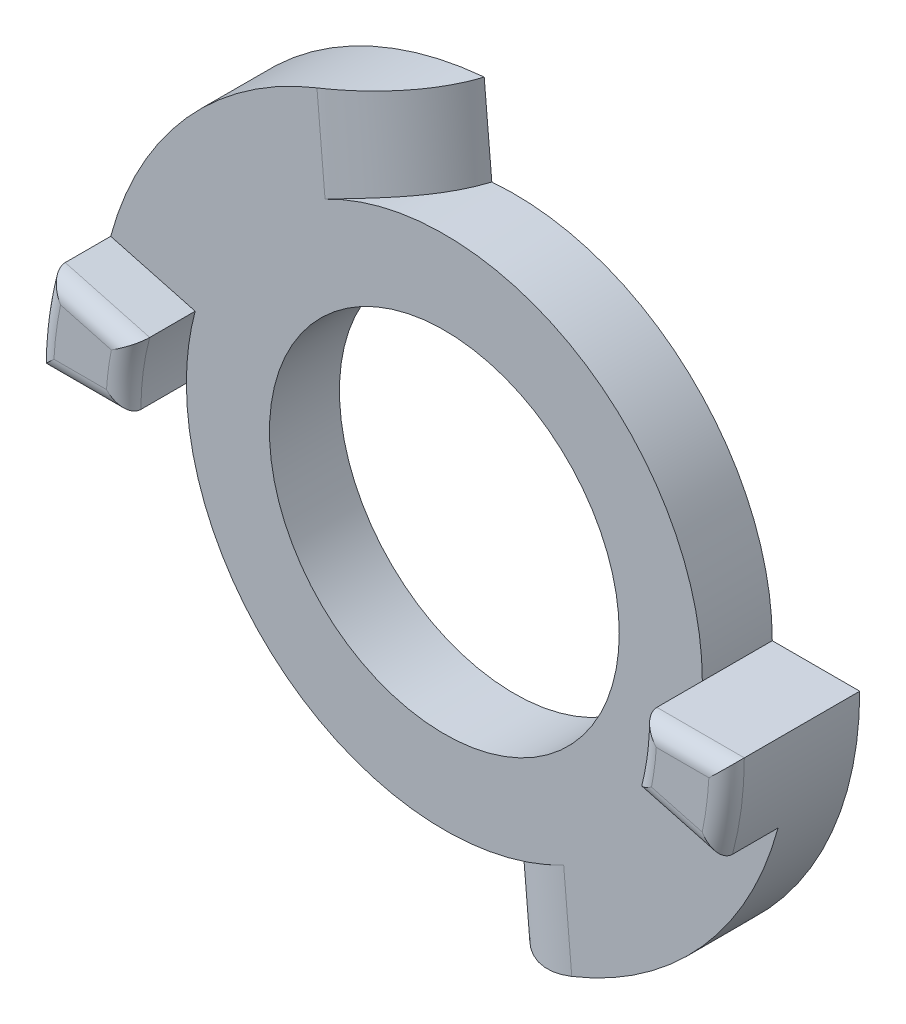
SolidWorks part; units mm, degrees
ref_plane "Front Plane" through (0, 0, 0) normal (0, 0, 1) x (1, 0, 0)
ref_plane "Top Plane" through (0, 0, 0) normal (0, 1, 0) x (1, 0, 0)
ref_plane "Right Plane" through (0, 0, 0) normal (1, 0, 0) x (0, 0, -1)
sketch "Sketch2" plane through (0, 0, 0) normal (0, 0, 1) x (1, 0, 0)
  line L0 (0, 0) -> (-0.9273, 10.599)
  line L1 (0, 7.5) -> (0, 10) construction
  line L2 (0, 0) -> (1.0257, -11.7238)
  line L3 (0, -7.5) -> (0, -10) construction
  line L4 (-10, 0) -> (0, 0)
  line L5 (0, 0) -> (10.8115, 0)
  circle A1 centre (0, 0) radius 9.875
  circle A2 centre (0, 0) radius 5
  circle A3 centre (0, 0) radius 7.375
  arc A4 (0, 10) -> (-10, 0) centre (0, 0) ccw construction
  line M6 (3.4641, -6) -> (-3.4641, -6)
  line M7 (-3.4641, -6) -> (-6.9282, 0)
  line M8 (-6.9282, 0) -> (-3.4641, 6)
  line M9 (-3.4641, 6) -> (3.4641, 6)
  line M10 (3.4641, 6) -> (6.9282, 0)
  line M11 (6.9282, 0) -> (3.4641, -6)
  dimension "D1" = 19.75
  dimension "D2" = 10
  dimension "D5" = 14.75
  dimension "D3" = 5
  dimension "D4" = 5
extrude "Boss-Extrude1" add sketch "Sketch2" along normal blind 2 contours A3 L0 A1 L4 | A3 L2 A1 L5 | A2 L4 L2 M7 M6 | L4 A3 L2 M6 M7 | L0 A3 L4 M8 M9 | A2 L0 L4 M9 M8 | A2 L5 L0 M10 M9 | L5 A3 L0 M9 M10 | L2 A3 L5 M11 M6 | A2 L2 L5 M6 M11 region at (-3.8177, 3.5091, 0) region at (3.5104, 3.6704, 0) region at (3.8177, -3.5091, 0) region at (-3.5104, -3.6704, 0) region at (-4.6055, 4.209, 0) region at (-0.4753, 6.683, 0) region at (4.6055, -4.209, 0) region at (0.4753, -6.683, 0) region at (-5.8323, 5.3443, 0) region at (5.8323, -5.3443, 0)
fillet "Fillet1" radius 3 2 edges at (0.7517, -8.5922, 2) (-0.7517, 8.5922, 2)
sketch "Sketch3" plane through (0, 0, 2) normal (0, 0, 1) x (1, 0, 0)
  line L0 (0, 0) -> (-10.6311, 2.8486)
  line L1 (-10.6311, 2.8486) -> (11.0227, -2.9535)
  line L2 (-9.875, 0) -> (-7.375, 0) construction
  circle A0 centre (0, 0) radius 9.875
  circle A1 centre (0, 0) radius 7.375
  arc M7 (3.6423, -9.1788) -> (9.875, 0) centre (0, 0) ccw
  line M8 (9.875, 0) -> (7.375, 0)
  arc M11 (-3.6423, 9.1788) -> (-9.875, 0) centre (0, 0) ccw
  line M12 (-9.875, 0) -> (-7.375, 0)
  dimension "D1" = 15
extrude "Boss-Extrude2" add sketch "Sketch3" along normal blind 1.8 contours A1 L1 M11 M12 | A1 L1 M7 M8 region at (-8.5865, 1.1304, 2) region at (8.5865, -1.1304, 2)
fillet "Fillet2" radius 0.5 8 edges at (-7.3119, 0.9626, 3.8) (-8.3311, 2.2323, 3.8) (-9.7905, 1.2889, 3.8) (-8.625, 0, 3.8) (7.3119, -0.9626, 3.8) (8.3311, -2.2323, 3.8) (9.7905, -1.2889, 3.8) (8.625, 0, 3.8)
